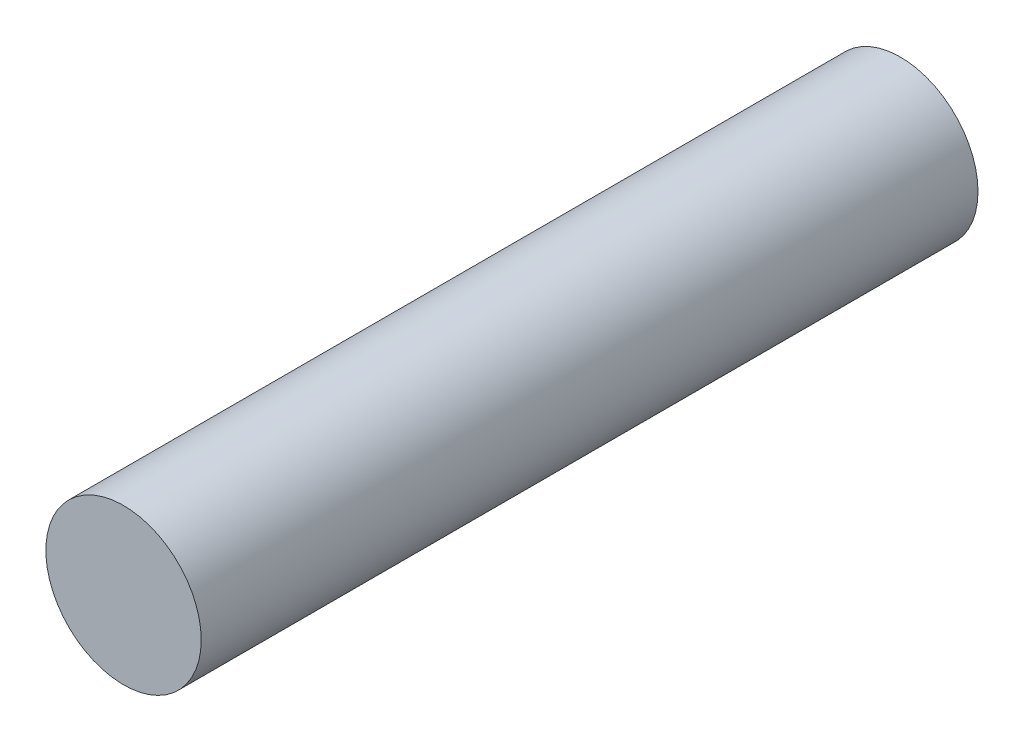
SolidWorks part; units mm, degrees
ref_plane "正面" through (0, 0, 0) normal (0, 0, 1) x (1, 0, 0)
ref_plane "平面" through (0, 0, 0) normal (0, 1, 0) x (1, 0, 0)
ref_plane "右側面" through (0, 0, 0) normal (1, 0, 0) x (0, 0, -1)
sketch "ｽｹｯﾁ1" plane through (0, 0, 0) normal (0, 0, 1) x (1, 0, 0)
  circle A0 centre (0, 0) radius 5
  dimension "D1" = 10
extrude "ﾎﾞｽ - 押し出し1" add sketch "ｽｹｯﾁ1" along normal blind 50
